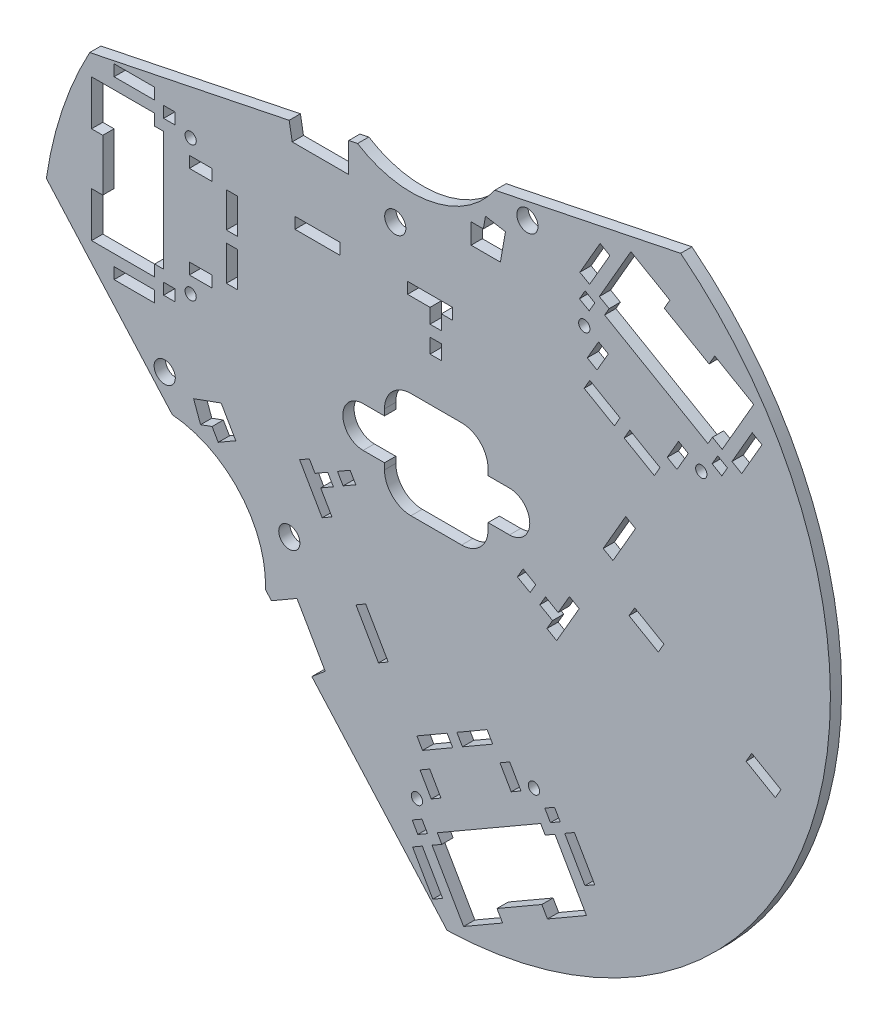
SolidWorks part; units mm, degrees
material "Balsa"
ref_plane "Plan de face" through (0, 0, 0) normal (0, 0, 1) x (1, 0, 0)
ref_plane "Plan de dessus" through (0, 0, 0) normal (0, 1, 0) x (1, 0, 0)
ref_plane "Plan de droite" through (0, 0, 0) normal (1, 0, 0) x (0, 0, -1)
sketch "Esquisse1" plane through (0, 0, 0) normal (0, 0, 1) x (1, 0, 0)
  circle A0 centre (148.0804, -12.1102) radius 175
extrude "Boss.-Extru.1" add sketch "Esquisse1" along normal blind 5
sketch "Esquisse2" plane through (0, 0, 0) normal (0, 0, -1) x (-1, 0, 0)
  line L0 (-155.3118, 53.7774) -> (-135.3118, 53.7774)
  line L1 (-150.3118, 37.2774) -> (-145.3118, 37.2774)
  line L2 (-150.3118, 37.2774) -> (-150.3118, 30.7774)
  line L3 (-150.3118, 30.7774) -> (-145.3118, 30.7774)
  line L4 (-145.3118, 37.2774) -> (-145.3118, 30.7774)
  line L5 (-105.3118, 53.7774) -> (-85.3118, 53.7774)
  line L6 (-105.3118, 53.7774) -> (-105.3118, 48.7774)
  line L7 (-105.3118, 48.7774) -> (-85.3118, 48.7774)
  line L8 (-85.3118, 53.7774) -> (-85.3118, 48.7774)
  line L9 (-59.86, 48.7774) -> (-54.86, 48.7774)
  line L10 (-59.86, 48.7774) -> (-59.86, 33.2774)
  line L11 (-59.86, 33.2774) -> (-54.86, 33.2774)
  line L12 (-54.86, 48.7774) -> (-54.86, 33.2774)
  line L13 (-59.86, 28.2774) -> (-54.86, 28.2774)
  line L14 (-59.86, 28.2774) -> (-59.86, 12.7774)
  line L15 (-59.86, 12.7774) -> (-54.86, 12.7774)
  line L16 (-54.86, 28.2774) -> (-54.86, 12.7774)
  line L17 (-48.43, 12.7774) -> (-38.43, 12.7774)
  line L18 (-48.43, 12.7774) -> (-48.43, 7.7774)
  line L19 (-48.43, 7.7774) -> (-38.43, 7.7774)
  line L20 (-38.43, 12.7774) -> (-38.43, 7.7774)
  line L21 (-32, -0.7226) -> (-27, -0.7226)
  line L22 (-32, -0.7226) -> (-32, -5.7226)
  line L23 (-32, -5.7226) -> (-27, -5.7226)
  line L24 (-27, -0.7226) -> (-27, -5.7226)
  line L25 (-23, -5.7226) -> (-5, -5.7226)
  line L26 (-23, -5.7226) -> (-23, -10.7226)
  line L27 (-23, -10.7226) -> (-5, -10.7226)
  line L28 (-5, -5.7226) -> (-5, -10.7226)
  line L29 (0, -0.7226) -> (5, -0.7226)
  line L30 (0, -0.7226) -> (0, 19.2774)
  line L31 (0, 19.2774) -> (5, 19.2774)
  line L32 (5, -0.7226) -> (5, 19.2774)
  line L33 (0, 42.2774) -> (5, 42.2774)
  line L34 (0, 42.2774) -> (0, 62.2774)
  line L35 (0, 62.2774) -> (5, 62.2774)
  line L36 (5, 42.2774) -> (5, 62.2774)
  line L37 (-23, 67.2774) -> (-5, 67.2774)
  line L38 (-23, 67.2774) -> (-23, 72.2774)
  line L39 (-23, 72.2774) -> (-5, 72.2774)
  line L40 (-5, 67.2774) -> (-5, 72.2774)
  line L41 (-27, 67.2774) -> (-32, 67.2774)
  line L42 (-27, 67.2774) -> (-27, 62.2774)
  line L43 (-27, 62.2774) -> (-32, 62.2774)
  line L44 (-32, 67.2774) -> (-32, 62.2774)
  line L45 (-38.43, 53.7774) -> (-48.43, 53.7774)
  line L46 (-38.43, 53.7774) -> (-38.43, 48.7774)
  line L47 (-38.43, 48.7774) -> (-48.43, 48.7774)
  line L48 (-48.43, 53.7774) -> (-48.43, 48.7774)
  line L49 (-135.3118, 53.7774) -> (-135.3118, 48.7774)
  line L50 (-135.3118, 48.7774) -> (-145.3118, 48.7774)
  line L51 (-135.3118, 48.7774) -> (-155.3118, 48.7774) construction
  line L52 (-145.3118, 48.7774) -> (-145.3118, 42.2774)
  line L53 (-145.3118, 42.2774) -> (-150.3118, 42.2774)
  line L54 (-150.3118, 42.2774) -> (-150.3118, 48.7774)
  line L55 (-150.3118, 48.7774) -> (-155.3118, 48.7774)
  line L56 (-155.3118, 48.7774) -> (-155.3118, 53.7774)
  line L57 (-87.4044, -38.7914) -> (-97.4044, -56.1119)
  line L58 (-104.1938, -34.8716) -> (-106.6938, -39.2017)
  line L59 (-104.1938, -34.8716) -> (-109.823, -31.6216)
  line L60 (-109.823, -31.6216) -> (-112.323, -35.9517)
  line L61 (-106.6938, -39.2017) -> (-112.323, -35.9517)
  line L62 (-112.4044, -82.0927) -> (-122.4044, -99.4132)
  line L63 (-112.4044, -82.0927) -> (-116.7345, -79.5927)
  line L64 (-116.7345, -79.5927) -> (-126.7345, -96.9132)
  line L65 (-122.4044, -99.4132) -> (-126.7345, -96.9132)
  line L66 (-139.4604, -118.9551) -> (-141.9604, -123.2852)
  line L67 (-139.4604, -118.9551) -> (-152.8838, -111.2051)
  line L68 (-152.8838, -111.2051) -> (-155.3838, -115.5352)
  line L69 (-141.9604, -123.2852) -> (-155.3838, -115.5352)
  line L70 (-157.2139, -108.7051) -> (-159.7139, -113.0352)
  line L71 (-157.2139, -108.7051) -> (-170.6373, -100.9551)
  line L72 (-170.6373, -100.9551) -> (-173.1373, -105.2852)
  line L73 (-159.7139, -113.0352) -> (-173.1373, -105.2852)
  line L74 (-176.3523, -110.8538) -> (-181.3523, -119.514)
  line L75 (-176.3523, -110.8538) -> (-180.6825, -108.3538)
  line L76 (-180.6825, -108.3538) -> (-185.6825, -117.014)
  line L77 (-181.3523, -119.514) -> (-185.6825, -117.014)
  line L78 (-196.2587, -118.3326) -> (-198.7587, -122.6627)
  line L79 (-196.2587, -118.3326) -> (-200.5888, -115.8326)
  line L80 (-200.5888, -115.8326) -> (-203.0888, -120.1627)
  line L81 (-198.7587, -122.6627) -> (-203.0888, -120.1627)
  line L82 (-205.0888, -123.6268) -> (-214.0888, -139.2153)
  line L83 (-205.0888, -123.6268) -> (-209.4189, -121.1268)
  line L84 (-209.4189, -121.1268) -> (-218.4189, -136.7153)
  line L85 (-214.0888, -139.2153) -> (-218.4189, -136.7153)
  line L86 (-212.2587, -146.0454) -> (-214.7587, -150.3755)
  line L87 (-212.2587, -146.0454) -> (-194.9382, -156.0454)
  line L88 (-194.9382, -156.0454) -> (-197.4382, -160.3755)
  line L89 (-214.7587, -150.3755) -> (-197.4382, -160.3755)
  line L90 (-175.0196, -167.5454) -> (-177.5196, -171.8755)
  line L91 (-175.0196, -167.5454) -> (-157.6991, -177.5454)
  line L92 (-157.6991, -177.5454) -> (-160.1991, -181.8755)
  line L93 (-177.5196, -171.8755) -> (-160.1991, -181.8755)
  line L94 (-141.869, -160.1268) -> (-150.869, -175.7153)
  line L95 (-141.869, -160.1268) -> (-137.5388, -162.6268)
  line L96 (-137.5388, -162.6268) -> (-146.5388, -178.2153)
  line L97 (-150.869, -175.7153) -> (-146.5388, -178.2153)
  line L98 (-139.869, -156.6627) -> (-137.369, -152.3326)
  line L99 (-139.869, -156.6627) -> (-144.1991, -154.1627)
  line L100 (-144.1991, -154.1627) -> (-141.6991, -149.8326)
  line L101 (-137.369, -152.3326) -> (-141.6991, -149.8326)
  line L102 (-145.8453, -140.014) -> (-140.8453, -131.3538)
  line L103 (-145.8453, -140.014) -> (-150.1754, -137.514)
  line L104 (-150.1754, -137.514) -> (-145.1754, -128.8538)
  line L105 (-140.8453, -131.3538) -> (-145.1754, -128.8538)
  line L106 (-97.4044, -56.1119) -> (-101.7345, -53.6119)
  line L107 (-101.7345, -53.6119) -> (-96.7345, -44.9517)
  line L108 (-96.7345, -44.9517) -> (-102.3637, -41.7017)
  line L109 (-102.3637, -41.7017) -> (-99.8637, -37.3716)
  line L110 (-99.8637, -37.3716) -> (-94.2345, -40.6216)
  line L111 (-94.2345, -40.6216) -> (-91.7345, -36.2914)
  line L112 (-91.7345, -36.2914) -> (-87.4044, -38.7914)
  line L113 (-201.5251, -51.3165) -> (-211.5251, -33.996)
  line L114 (-189.7357, -38.7364) -> (-192.2357, -34.4063)
  line L115 (-189.7357, -38.7364) -> (-184.1065, -35.4864)
  line L116 (-184.1065, -35.4864) -> (-186.6065, -31.1563)
  line L117 (-192.2357, -34.4063) -> (-186.6065, -31.1563)
  line L118 (-226.5251, -8.0153) -> (-236.5251, 9.3053)
  line L119 (-226.5251, -8.0153) -> (-222.195, -5.5153)
  line L120 (-222.195, -5.5153) -> (-232.195, 11.8053)
  line L121 (-236.5251, 9.3053) -> (-232.195, 11.8053)
  line L122 (-244.9209, 33.8472) -> (-247.4209, 38.1773)
  line L123 (-244.9209, 33.8472) -> (-231.4975, 41.5972)
  line L124 (-231.4975, 41.5972) -> (-233.9975, 45.9273)
  line L125 (-247.4209, 38.1773) -> (-233.9975, 45.9273)
  line L126 (-227.1673, 44.0972) -> (-229.6673, 48.4273)
  line L127 (-227.1673, 44.0972) -> (-213.7439, 51.8472)
  line L128 (-213.7439, 51.8472) -> (-216.2439, 56.1773)
  line L129 (-229.6673, 48.4273) -> (-216.2439, 56.1773)
  line L130 (-219.4589, 61.7458) -> (-224.4589, 70.4061)
  line L131 (-219.4589, 61.7458) -> (-215.1288, 64.2458)
  line L132 (-215.1288, 64.2458) -> (-220.1288, 72.9061)
  line L133 (-224.4589, 70.4061) -> (-220.1288, 72.9061)
  line L134 (-215.9826, 82.7246) -> (-218.4826, 87.0547)
  line L135 (-215.9826, 82.7246) -> (-211.6525, 85.2246)
  line L136 (-211.6525, 85.2246) -> (-214.1525, 89.5547)
  line L137 (-218.4826, 87.0547) -> (-214.1525, 89.5547)
  line L138 (-216.1525, 93.0188) -> (-225.1525, 108.6073)
  line L139 (-216.1525, 93.0188) -> (-211.8223, 95.5188)
  line L140 (-211.8223, 95.5188) -> (-220.8223, 111.1073)
  line L141 (-225.1525, 108.6073) -> (-220.8223, 111.1073)
  line L142 (-231.9826, 110.4374) -> (-234.4826, 114.7676)
  line L143 (-231.9826, 110.4374) -> (-249.3031, 100.4374)
  line L144 (-249.3031, 100.4374) -> (-251.8031, 104.7676)
  line L145 (-234.4826, 114.7676) -> (-251.8031, 104.7676)
  line L146 (-269.2217, 88.9374) -> (-271.7217, 93.2676)
  line L147 (-269.2217, 88.9374) -> (-286.5422, 78.9374)
  line L148 (-286.5422, 78.9374) -> (-289.0422, 83.2676)
  line L149 (-271.7217, 93.2676) -> (-289.0422, 83.2676)
  line L150 (-279.3723, 56.5188) -> (-288.3723, 72.1073)
  line L151 (-279.3723, 56.5188) -> (-283.7025, 54.0188)
  line L152 (-283.7025, 54.0188) -> (-292.7025, 69.6073)
  line L153 (-288.3723, 72.1073) -> (-292.7025, 69.6073)
  line L154 (-277.3723, 53.0547) -> (-274.8723, 48.7246)
  line L155 (-277.3723, 53.0547) -> (-273.0422, 55.5547)
  line L156 (-273.0422, 55.5547) -> (-270.5422, 51.2246)
  line L157 (-274.8723, 48.7246) -> (-270.5422, 51.2246)
  line L158 (-259.966, 49.9061) -> (-254.966, 41.2458)
  line L159 (-259.966, 49.9061) -> (-255.6359, 52.4061)
  line L160 (-255.6359, 52.4061) -> (-250.6359, 43.7458)
  line L161 (-254.966, 41.2458) -> (-250.6359, 43.7458)
  line L162 (-211.5251, -33.996) -> (-207.195, -31.496)
  line L163 (-207.195, -31.496) -> (-202.195, -40.1563)
  line L164 (-202.195, -40.1563) -> (-196.5658, -36.9063)
  line L165 (-196.5658, -36.9063) -> (-194.0658, -41.2364)
  line L166 (-194.0658, -41.2364) -> (-199.695, -44.4864)
  line L167 (-199.695, -44.4864) -> (-197.195, -48.8165)
  line L168 (-197.195, -48.8165) -> (-201.5251, -51.3165)
  point P204 (-148.0804, -12.1102)
  dimension "D1" = 3
extrude "Enlèv. mat.-Extru.1" cut sketch "Esquisse2" against normal blind 5
sketch "Esquisse3" plane through (0, 0, 0) normal (0, 0, -1) x (-1, 0, 0)
  line L0 (-59.86, 33.2774) -> (-59.86, 28.2774) construction
  line L1 (-59.86, 30.7774) -> (32.4397, 30.7774) construction
  line L2 (0, -0.7226) -> (-23, -0.7226)
  line L3 (-23, -0.7226) -> (-23, 4.2774)
  line L4 (-23, 4.2774) -> (-27, 4.2774)
  line L5 (-23, 57.2774) -> (-27, 57.2774)
  line L6 (-23, 62.2774) -> (-23, 57.2774)
  line L7 (0, 62.2774) -> (-23, 62.2774)
  line L8 (-27, 57.2774) -> (-27, 4.2774)
  line L9 (0, -0.7226) -> (0, 62.2774)
  line L10 (-212.2587, -146.0454) -> (-200.7587, -126.1268)
  line L11 (-200.7587, -126.1268) -> (-196.4286, -128.6268)
  line L12 (-196.4286, -128.6268) -> (-194.4286, -125.1627)
  line L13 (-150.5292, -155.1268) -> (-148.5292, -151.6627)
  line L14 (-146.1991, -157.6268) -> (-150.5292, -155.1268)
  line L15 (-157.6991, -177.5454) -> (-146.1991, -157.6268)
  line L16 (-148.5292, -151.6627) -> (-194.4286, -125.1627)
  line L17 (-212.2587, -146.0454) -> (-157.6991, -177.5454)
  line L18 (-152.8838, -111.2051) -> (-157.2139, -108.7051) construction
  line L19 (-155.0489, -109.9551) -> (-201.1987, -189.889) construction
  line L20 (-231.9826, 110.4374) -> (-220.4826, 90.5188)
  line L21 (-220.4826, 90.5188) -> (-224.8127, 88.0188)
  line L22 (-224.8127, 88.0188) -> (-222.8127, 84.5547)
  line L23 (-270.7121, 61.5188) -> (-268.7121, 58.0547)
  line L24 (-275.0422, 59.0188) -> (-270.7121, 61.5188)
  line L25 (-286.5422, 78.9374) -> (-275.0422, 59.0188)
  line L26 (-268.7121, 58.0547) -> (-222.8127, 84.5547)
  line L27 (-231.9826, 110.4374) -> (-286.5422, 78.9374)
  line L28 (-231.4975, 41.5972) -> (-227.1673, 44.0972) construction
  line L29 (-229.3324, 42.8472) -> (-275.4822, 122.781) construction
  point P42 (-148.0804, -12.1102)
  dimension "D1" = 5
  dimension "D2" = 4
  dimension "D3" = 23
  dimension "D4" = 3
extrude "Enlèv. mat.-Extru.2" cut sketch "Esquisse3" against normal blind 5
sketch "Esquisse4" plane through (0, 0, 0) normal (0, 0, -1) x (-1, 0, 0)
  line L0 (-32, 67.2774) -> (-32, 62.2774) construction
  line L1 (-38.43, 53.7774) -> (-48.43, 53.7774) construction
  line L2 (-27, 30.7774) -> (-93.5454, 30.7774) construction
  line L3 (-27, 57.2774) -> (-27, 4.2774) construction
  line L4 (-171.4789, -138.4127) -> (-138.2062, -80.7827) construction
  line L5 (-245.7624, 71.3047) -> (-212.4897, 13.6748) construction
  circle A0 centre (-39, 60.7774) radius 2.5
  circle A1 centre (-39, 0.7774) radius 2.5
  circle A2 centre (-139.4981, -143.0204) radius 2.5
  circle A3 centre (-191.4596, -113.0204) radius 2.5
  circle A4 centre (-265.7432, 45.9124) radius 2.5
  circle A5 centre (-213.7816, 75.9124) radius 2.5
  point P27 (-148.0804, -12.1102)
  dimension "D1" = 7
  dimension "D2" = 7
  dimension "D3" = 3
extrude "Enlèv. mat.-Extru.3" cut sketch "Esquisse4" against normal blind 5
sketch "Esquisse5" plane through (0, 0, 0) normal (0, 0, -1) x (-1, 0, 0)
  line L0 (9.513, 70.4436) -> (-93.4749, 91.6327)
  line L1 (-315.6991, 137.3538) -> (-290.787, 258.4375)
  line L2 (-290.787, 258.4375) -> (34.4251, 191.5273)
  line L3 (34.4251, 191.5273) -> (9.513, 70.4436)
  line L4 (-233.6714, -25.6375) -> (-246.6617, -33.1375)
  line L5 (-179.3609, 109.3031) -> (-315.6991, 137.3538)
  line L6 (-94.86, 83.7774) -> (-174.86, 83.7774)
  line L7 (-174.86, 83.7774) -> (-179.3609, 109.3031)
  line L8 (-233.6714, -25.6375) -> (-236.1714, -21.3074)
  line L9 (-93.4749, 91.6327) -> (-94.86, 83.7774)
  line L10 (-155.3834, -189.8669) -> (-85.5392, -111.2714)
  line L11 (65.1685, 58.3199) -> (157.574, -23.7965)
  line L12 (26.9196, -12.1102) -> (-148.0804, -12.1102) construction
  line L13 (157.574, -23.7965) -> (-62.9779, -271.9834)
  line L14 (-62.9779, -271.9834) -> (-155.3834, -189.8669)
  line L15 (-246.6617, -33.1375) -> (-249.1617, -28.8074)
  line L16 (-27.2932, -45.7272) -> (65.1685, 58.3199)
  line L17 (-91.6495, -106.1442) -> (-51.6495, -36.8622)
  line L18 (-51.6495, -36.8622) -> (-27.2932, -45.7272)
  line L19 (-236.1714, -21.3074) -> (-249.1617, -28.8074)
  line L20 (-85.5392, -111.2714) -> (-91.6495, -106.1442)
  line L21 (-148.0804, -12.1102) -> (-235.5804, -163.6646) construction
  line L22 (-93.4749, 91.6327) -> (-179.3609, 109.3031) construction
  line L23 (-139.86, 83.7774) -> (-139.86, 101.1761) construction
  line L24 (-285.6329, -55.6375) -> (-298.6233, -63.1375)
  line L25 (-285.6329, -55.6375) -> (-288.1329, -51.3074)
  line L26 (-298.6233, -63.1375) -> (-301.1233, -58.8074)
  line L27 (-288.1329, -51.3074) -> (-301.1233, -58.8074)
  line L28 (-211.5251, -33.996) -> (-201.5251, -51.3165) construction
  line L29 (-283.7025, 54.0188) -> (-279.3723, 56.5188) construction
  circle A0 centre (-188.5408, 103.7774) radius 4.7
  circle A1 centre (-129.86, 73.7774) radius 4.7
  circle A2 centre (-27.4886, -35.0143) radius 4.7
  circle A3 centre (-82.8098, -70.8333) radius 4.7
  point P15 (-148.0804, -12.1102)
  point P35 (-148.0804, -12.1102)
  dimension "D2" = 9.4
  dimension "D3" = 9.4
  dimension "D4" = 100
  dimension "D5" = 100
  dimension "D6" = 5
  dimension "D7" = 45
  dimension "D8" = 15
  dimension "D9" = 80
  dimension "D10" = 35
  dimension "D11" = 85.8876
  dimension "D12" = 58.6808
  dimension "D13" = 30
  dimension "D14" = 10
  dimension "D15" = 11.626
  dimension "D16" = 18.2204
  dimension "D18" = 17.3986
  dimension "D19" = 15
  dimension "D20" = 45
  dimension "D21" = 15
  dimension "D22" = 89
  dimension "D17" = 2
extrude "Enlèv. mat.-Extru.4" cut sketch "Esquisse5" against normal blind 5
sketch "Esquisse6" plane through (0, 0, 0) normal (0, 0, -1) x (-1, 0, 0)
  line L7 (-72.2193, -96.2825) -> (-85.5392, -111.2714)
  line L8 (-85.5392, -111.2714) -> (-94.4781, -107.3647)
  line L9 (-94.4781, -107.3647) -> (-52.0208, -31.4132)
  line L10 (-52.0208, -31.4132) -> (-27.2932, -45.7272)
  line L11 (-27.2932, -45.7272) -> (-30.866, -49.7477)
  line L13 (-113.1156, 95.6736) -> (-93.4749, 91.6327)
  line L14 (-93.4749, 91.6327) -> (-92.3887, 81.938)
  line L15 (-92.3887, 81.938) -> (-179.3934, 80.7314)
  line L16 (-179.3934, 80.7314) -> (-179.3609, 109.3031)
  line L17 (-179.3609, 109.3031) -> (-174.0926, 108.2192)
  arc A0 (-72.2193, -96.2825) -> (-30.866, -49.7477) centre (-27.2507, -94.6022) cw
  arc A2 (-113.1156, 95.6736) -> (-174.0926, 108.2192) centre (-137.0551, 133.7774) cw
  point P3 (-148.0804, -12.1102)
  point P21 (-148.0804, -12.1102)
  dimension "D1" = 45
  dimension "D2" = 2
extrude "Boss.-Extru.2" add sketch "Esquisse6" against normal blind 5
sketch "Esquisse7" plane through (0, 0, 0) normal (0, 0, -1) x (-1, 0, 0)
  line L0 (-109.1977, 94.8675) -> (-109.1977, 81.7774)
  line L1 (-113.1156, 95.6736) -> (5.8145, 71.2045) construction
  line L2 (-109.1977, 81.7774) -> (-84.1003, 81.7774)
  line L3 (-84.1003, 81.7774) -> (-82.7516, 89.4264)
  line L4 (-82.7516, 89.4264) -> (-109.1977, 94.8675)
  line L5 (26.9196, -12.1102) -> (-148.0804, -12.1102) construction
  line L6 (-74.8764, -99.2725) -> (-86.2127, -92.7274)
  line L7 (-163.5382, 81.7774) -> (-176.5382, 81.7774)
  line L8 (-176.5382, 81.7774) -> (-178.7956, 94.5799)
  line L9 (-178.7956, 94.5799) -> (-169.9324, 96.1428)
  line L10 (-169.9324, 96.1428) -> (-168.9863, 90.7774)
  line L12 (-168.9863, 90.7774) -> (-163.5382, 90.7774)
  line L13 (-163.5382, 90.7774) -> (-163.5382, 81.7774)
  line L14 (-86.2127, -92.7274) -> (-98.7614, -114.4624)
  line L15 (-98.7614, -114.4624) -> (-92.8116, -119.4549)
  line L16 (-92.8116, -119.4549) -> (-74.8764, -99.2725)
  line L17 (-59.0425, -45.6672) -> (-52.5425, -34.4088)
  line L18 (-52.5425, -34.4088) -> (-40.3265, -38.8551)
  line L19 (-40.3265, -38.8551) -> (-43.4047, -47.3123)
  line L20 (-43.4047, -47.3123) -> (-48.5242, -45.449)
  line L21 (-48.5242, -45.449) -> (-51.2483, -50.1672)
  line L22 (-51.2483, -50.1672) -> (-59.0425, -45.6672)
  point P14 (-148.0804, -12.1102)
  point P31 (-148.0804, -12.1102)
  dimension "D1" = 80
  dimension "D2" = 13.0901
  dimension "D3" = 4
  dimension "D4" = 27
  dimension "D5" = 20
  dimension "D6" = 9
  dimension "D7" = 9
  dimension "D8" = 7
  dimension "D9" = 13
  dimension "D10" = 13
  dimension "D11" = 2
extrude "Enlèv. mat.-Extru.5" cut sketch "Esquisse7" against normal blind 5
sketch "Esquisse9" plane through (0, 0, 5) normal (0, 0, 1) x (1, 0, 0)
  line L0 (171.0804, 11.3898) -> (125.0804, 11.3898) construction
  line L1 (171.0804, 11.3898) -> (171.0804, -35.6102) construction
  line L2 (125.0804, 11.3898) -> (125.0804, -35.6102) construction
  line L3 (171.0804, -35.6102) -> (125.0804, -35.6102) construction
  line L4 (145.3118, 48.7774) -> (135.3118, 48.7774) construction
  line L5 (171.0804, 11.3898) -> (125.0804, -35.6102) construction
  line L6 (125.0804, 11.3898) -> (171.0804, -35.6102) construction
  line L7 (180.5804, -12.1102) -> (115.5804, -12.1102) construction
  line L8 (180.5804, -21.1102) -> (171.0804, -21.1102)
  line L9 (180.5804, -3.1102) -> (171.0804, -3.1102)
  line L10 (159.3304, 11.3898) -> (136.8304, 11.3898)
  line L11 (125.0804, -0.3602) -> (125.0804, -3.1102)
  line L12 (125.0804, -23.8602) -> (125.0804, -21.1102)
  line L13 (159.3304, -35.6102) -> (136.8304, -35.6102)
  line L14 (171.0804, -0.3602) -> (171.0804, -3.1102)
  line L15 (171.0804, -23.8602) -> (171.0804, -21.1102)
  line L16 (125.0804, -3.1102) -> (115.5804, -3.1102)
  line L17 (125.0804, -21.1102) -> (115.5804, -21.1102)
  arc A0 (171.0804, -0.3602) -> (159.3304, 11.3898) centre (159.3304, -0.3602) ccw
  arc A1 (159.3304, -35.6102) -> (171.0804, -23.8602) centre (159.3304, -23.8602) ccw
  arc A2 (125.0804, -23.8602) -> (136.8304, -35.6102) centre (136.8304, -23.8602) ccw
  arc A3 (136.8304, 11.3898) -> (125.0804, -0.3602) centre (136.8304, -0.3602) ccw
  arc A5 (180.5804, -21.1102) -> (180.5804, -3.1102) centre (180.5804, -12.1102) ccw
  arc A6 (115.5804, -3.1102) -> (115.5804, -21.1102) centre (115.5804, -12.1102) ccw
  point P4 (148.0804, -12.1102)
  point P14 (148.0804, -12.1102)
  dimension "D1" = 46
  dimension "D2" = 47
  dimension "D3" = 11.75
  dimension "D4" = 9
  dimension "D5" = 65
  dimension "D6" = 32.5
extrude "Enlèv. mat.-Extru.6" cut sketch "Esquisse9" against normal blind 10
